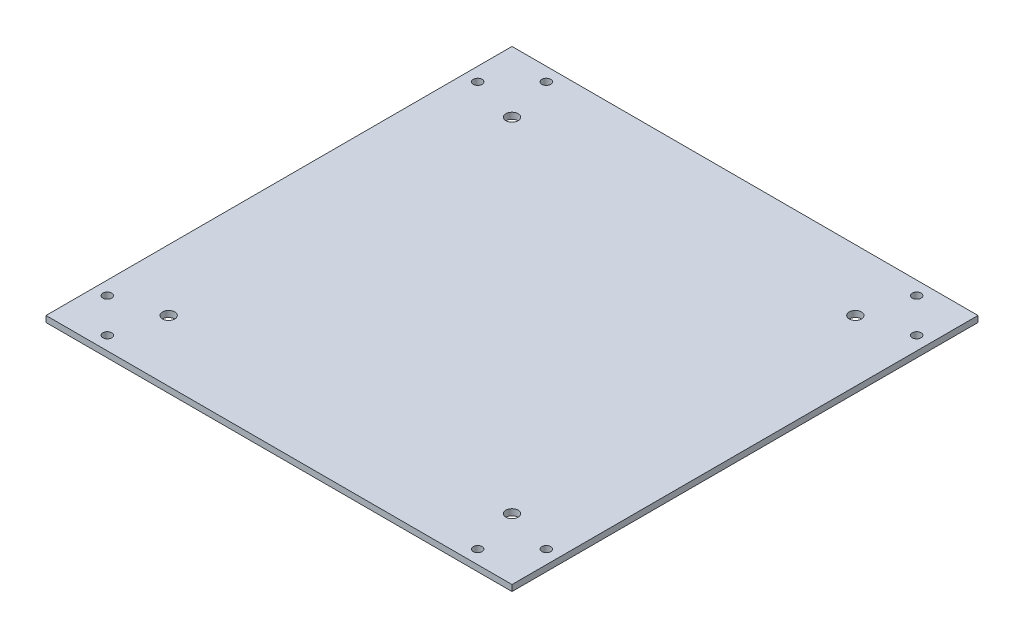
SolidWorks part; units mm, degrees
ref_plane "Front Plane" through (0, 0, 0) normal (0, 0, 1) x (1, 0, 0)
ref_plane "Top Plane" through (0, 0, 0) normal (0, 1, 0) x (1, 0, 0)
ref_plane "Right Plane" through (0, 0, 0) normal (1, 0, 0) x (0, 0, -1)
sketch "Sketch1" plane through (0, 0, 0) normal (0, 1, 0) x (1, 0, 0)
  line L1 (0, 0) -> (241.3, 0)
  line L2 (0, 0) -> (0, 241.3)
  line L3 (0, 241.3) -> (241.3, 241.3)
  line L4 (241.3, 0) -> (241.3, 241.3)
  dimension "9.5" = 241.3
  dimension "D2" = 241.3
extrude "Boss-Extrude1" add sketch "Sketch1" along normal blind 3.175
sketch "Sketch2" plane through (0, 3.175, 0) normal (0, 1, 0) x (1, 0, 0)
  line L0 (0, 0) -> (241.3, 0) construction
  line L1 (241.3, 0) -> (241.3, 241.3) construction
  line L2 (0, 0) -> (241.3, 241.3) construction
  line L3 (0, 241.3) -> (0, 0) construction
  circle A0 centre (234.315, 24.765) radius 2.286
  circle A1 centre (216.535, 6.985) radius 2.286
  circle A2 centre (6.985, 24.765) radius 2.286
  circle A3 centre (24.765, 6.985) radius 2.286
  circle A4 centre (24.765, 234.315) radius 2.286
  circle A5 centre (6.985, 216.535) radius 2.286
  circle A6 centre (234.315, 216.535) radius 2.286
  circle A7 centre (216.535, 234.315) radius 2.286
  circle A8 centre (209.55, 31.75) radius 3.175
  circle A9 centre (31.75, 31.75) radius 3.175
  circle A10 centre (31.75, 209.55) radius 3.175
  circle A11 centre (209.55, 209.55) radius 3.175
  point P10 (120.65, 120.65)
  dimension "D2" = 4.572
  dimension "D9" = 6.35
  dimension "D10" = 31.75
  dimension "D11" = 31.75
  dimension "D1" = 6.985
  dimension "D3" = 24.765
  dimension "D4" = 6.985
  dimension "D5" = 24.765
  dimension "D7" = 24.765
  dimension "D8" = 24.765
  dimension "D6" = 4
extrude "Cut-Extrude1" cut sketch "Sketch2" against normal through all
